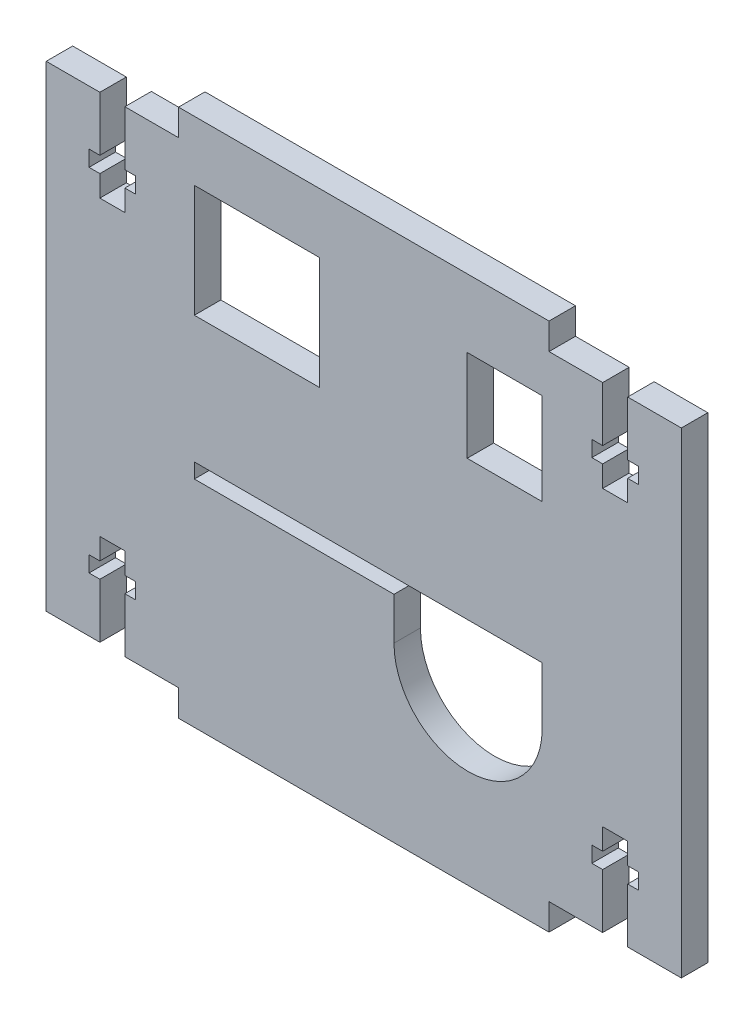
SolidWorks part; units mm, degrees
ref_plane "Front Plane" through (0, 0, 0) normal (0, 0, 1) x (1, 0, 0)
ref_plane "Top Plane" through (0, 0, 0) normal (0, 1, 0) x (1, 0, 0)
ref_plane "Right Plane" through (0, 0, 0) normal (1, 0, 0) x (0, 0, -1)
sketch "Sketch1" plane through (0, 0, 0) normal (0, 0, 1) x (1, 0, 0)
  line L1 (-38.1, -31.75) -> (38.1, -31.75)
  line L2 (-38.1, -31.75) -> (-38.1, 31.75)
  line L3 (-38.1, 31.75) -> (38.1, 31.75)
  line L4 (38.1, -31.75) -> (38.1, 31.75)
  line L5 (-38.1, -31.75) -> (38.1, 31.75) construction
  line L6 (-38.1, 31.75) -> (38.1, -31.75) construction
  point P0 (0, 0)
  dimension "D1" = 76.2
  dimension "D2" = 63.5
extrude "Boss-Extrude1" add sketch "Sketch1" along normal blind 3.175
sketch "Sketch2" plane through (0, 0, 0) normal (0, 0, -1) x (-1, 0, 0)
  line L0 (-38.1, 0) -> (38.1, 0) construction
  line L1 (-38.1, -31.75) -> (-22.225, -31.75)
  line L2 (-38.1, -31.75) -> (-38.1, -28.575)
  line L3 (-38.1, -28.575) -> (-22.225, -28.575)
  line L4 (-22.225, -31.75) -> (-22.225, -28.575)
  line L5 (38.1, -31.75) -> (22.225, -31.75)
  line L6 (38.1, -31.75) -> (38.1, -28.575)
  line L7 (38.1, -28.575) -> (22.225, -28.575)
  line L8 (22.225, -31.75) -> (22.225, -28.575)
  line L9 (-38.1, -31.75) -> (-38.1, 31.75) construction
  line L10 (38.1, 31.75) -> (38.1, -31.75) construction
  line L11 (22.225, 31.75) -> (22.225, 28.575)
  line L12 (38.1, 28.575) -> (22.225, 28.575)
  line L13 (38.1, 31.75) -> (38.1, 28.575)
  line L14 (38.1, 31.75) -> (22.225, 31.75)
  line L15 (-22.225, 31.75) -> (-22.225, 28.575)
  line L16 (-38.1, 28.575) -> (-22.225, 28.575)
  line L17 (-38.1, 31.75) -> (-38.1, 28.575)
  line L18 (-38.1, 31.75) -> (-22.225, 31.75)
  dimension "D1" = 3.175
  dimension "D2" = 44.45
extrude "Cut-Extrude1" cut sketch "Sketch2" against normal through all
sketch "Sketch3" plane through (0, 0, 3.175) normal (0, 0, 1) x (1, 0, 0)
  line L0 (31.6625, -17.575) -> (31.6625, -20.125)
  line L1 (31.6625, -17.575) -> (28.6625, -17.575)
  line L2 (31.6625, -28.575) -> (28.6625, -28.575)
  line L3 (28.6625, -17.575) -> (28.6625, -20.125)
  line L4 (31.6625, -17.575) -> (28.6625, -28.575) construction
  line L5 (31.6625, -28.575) -> (28.6625, -17.575) construction
  line L6 (28.6625, -22.025) -> (28.6625, -28.575)
  line L7 (27.3625, -22.025) -> (27.3625, -20.125)
  line L8 (27.3625, -22.025) -> (28.6625, -22.025)
  line L9 (32.9625, -22.025) -> (32.9625, -20.125)
  line L10 (27.3625, -20.125) -> (28.6625, -20.125)
  line L11 (27.3625, -22.025) -> (32.9625, -20.125) construction
  line L12 (32.9625, -22.025) -> (27.3625, -20.125) construction
  line L13 (31.6625, -22.025) -> (31.6625, -28.575)
  line L14 (28.6625, -20.125) -> (28.6625, -22.025) construction
  line L15 (31.6625, -17.575) -> (31.6625, -22.025) construction
  line L16 (31.6625, -22.025) -> (32.9625, -22.025)
  line L17 (31.6625, -20.125) -> (32.9625, -20.125)
  line L18 (28.6625, -20.125) -> (31.6625, -20.125) construction
  line L19 (31.6625, -22.025) -> (28.6625, -22.025) construction
  line L20 (22.225, -28.575) -> (38.1, -28.575) construction
  line L21 (0, 31.75) -> (0, -31.75) construction
  line L22 (22.225, 31.75) -> (-22.225, 31.75) construction
  line L23 (-22.225, -31.75) -> (22.225, -31.75) construction
  line L24 (-31.6625, -22.025) -> (-28.6625, -22.025) construction
  line L25 (-28.6625, -20.125) -> (-31.6625, -20.125) construction
  line L26 (-31.6625, -17.575) -> (-31.6625, -22.025) construction
  line L27 (-28.6625, -20.125) -> (-28.6625, -22.025) construction
  line L28 (-32.9625, -22.025) -> (-27.3625, -20.125) construction
  line L29 (-27.3625, -22.025) -> (-32.9625, -20.125) construction
  line L30 (-31.6625, -28.575) -> (-28.6625, -17.575) construction
  line L31 (-31.6625, -17.575) -> (-28.6625, -28.575) construction
  line L32 (-31.6625, -20.125) -> (-32.9625, -20.125)
  line L33 (-31.6625, -22.025) -> (-32.9625, -22.025)
  line L34 (-31.6625, -22.025) -> (-31.6625, -28.575)
  line L35 (-27.3625, -20.125) -> (-28.6625, -20.125)
  line L36 (-32.9625, -22.025) -> (-32.9625, -20.125)
  line L37 (-27.3625, -22.025) -> (-28.6625, -22.025)
  line L38 (-27.3625, -22.025) -> (-27.3625, -20.125)
  line L39 (-28.6625, -22.025) -> (-28.6625, -28.575)
  line L40 (-28.6625, -17.575) -> (-28.6625, -20.125)
  line L41 (-31.6625, -28.575) -> (-28.6625, -28.575)
  line L42 (-31.6625, -17.575) -> (-28.6625, -17.575)
  line L43 (-31.6625, -17.575) -> (-31.6625, -20.125)
  line L44 (-38.1, 0) -> (38.1, 0) construction
  line L45 (-38.1, 28.575) -> (-38.1, -28.575) construction
  line L46 (38.1, -28.575) -> (38.1, 28.575) construction
  line L47 (31.6625, 22.025) -> (28.6625, 22.025) construction
  line L48 (28.6625, 20.125) -> (31.6625, 20.125) construction
  line L49 (31.6625, 17.575) -> (31.6625, 22.025) construction
  line L50 (28.6625, 20.125) -> (28.6625, 22.025) construction
  line L51 (32.9625, 22.025) -> (27.3625, 20.125) construction
  line L52 (27.3625, 22.025) -> (32.9625, 20.125) construction
  line L53 (31.6625, 28.575) -> (28.6625, 17.575) construction
  line L54 (31.6625, 17.575) -> (28.6625, 28.575) construction
  line L55 (31.6625, 20.125) -> (32.9625, 20.125)
  line L56 (31.6625, 22.025) -> (32.9625, 22.025)
  line L57 (31.6625, 22.025) -> (31.6625, 28.575)
  line L58 (27.3625, 20.125) -> (28.6625, 20.125)
  line L59 (32.9625, 22.025) -> (32.9625, 20.125)
  line L60 (27.3625, 22.025) -> (28.6625, 22.025)
  line L61 (27.3625, 22.025) -> (27.3625, 20.125)
  line L62 (28.6625, 22.025) -> (28.6625, 28.575)
  line L63 (28.6625, 17.575) -> (28.6625, 20.125)
  line L64 (31.6625, 28.575) -> (28.6625, 28.575)
  line L65 (31.6625, 17.575) -> (28.6625, 17.575)
  line L66 (31.6625, 17.575) -> (31.6625, 20.125)
  line L67 (-31.6625, 17.575) -> (-28.6625, 28.575) construction
  line L68 (-31.6625, 28.575) -> (-28.6625, 17.575) construction
  line L69 (-27.3625, 22.025) -> (-32.9625, 20.125) construction
  line L70 (-32.9625, 22.025) -> (-27.3625, 20.125) construction
  line L71 (-28.6625, 20.125) -> (-28.6625, 22.025) construction
  line L72 (-31.6625, 17.575) -> (-31.6625, 22.025) construction
  line L73 (-28.6625, 20.125) -> (-31.6625, 20.125) construction
  line L74 (-31.6625, 22.025) -> (-28.6625, 22.025) construction
  line L75 (-31.6625, 17.575) -> (-31.6625, 20.125)
  line L76 (-31.6625, 17.575) -> (-28.6625, 17.575)
  line L77 (-31.6625, 28.575) -> (-28.6625, 28.575)
  line L78 (-28.6625, 17.575) -> (-28.6625, 20.125)
  line L79 (-28.6625, 22.025) -> (-28.6625, 28.575)
  line L80 (-27.3625, 22.025) -> (-27.3625, 20.125)
  line L81 (-27.3625, 22.025) -> (-28.6625, 22.025)
  line L82 (-32.9625, 22.025) -> (-32.9625, 20.125)
  line L83 (-27.3625, 20.125) -> (-28.6625, 20.125)
  line L84 (-31.6625, 22.025) -> (-31.6625, 28.575)
  line L85 (-31.6625, 22.025) -> (-32.9625, 22.025)
  line L86 (-31.6625, 20.125) -> (-32.9625, 20.125)
  point P0 (30.1625, -28.575)
  point P5 (30.1625, -21.075)
  point P35 (-30.1625, -21.075)
  point P36 (-30.1625, -28.575)
  point P55 (30.1625, 21.075)
  point P56 (30.1625, 28.575)
  point P69 (-30.1625, 28.575)
  point P70 (-30.1625, 21.075)
  dimension "D1" = 11
  dimension "D2" = 5.6
  dimension "D3" = 1.9
  dimension "D4" = 3.5
  dimension "D5" = 3
extrude "Cut-Extrude2" cut sketch "Sketch3" against normal through all
sketch "Sketch4" plane through (0, 0, 3.175) normal (0, 0, 1) x (1, 0, 0)
  line L0 (-18.0257, 12.575) -> (-7.6257, 12.575) construction
  line L1 (-20.3257, 11.075) -> (-5.3257, 11.075)
  line L2 (-20.3257, 11.075) -> (-20.3257, 24.575)
  line L3 (-20.3257, 24.575) -> (-5.3257, 24.575)
  line L4 (-5.3257, 11.075) -> (-5.3257, 24.575)
  line L5 (-18.8257, 12.975) -> (-18.8257, 23.075) construction
  line L6 (-6.8257, 12.975) -> (-6.8257, 23.075) construction
  line L7 (-18.5257, 23.075) -> (-7.1257, 23.075) construction
  line L8 (21.4041, 12.575) -> (12.4041, 12.575) construction
  line L9 (21.4041, 12.575) -> (12.4041, 12.575)
  line L10 (21.4041, 12.575) -> (21.4041, 23.575)
  line L11 (21.4041, 23.575) -> (12.4041, 23.575)
  line L12 (12.4041, 12.575) -> (12.4041, 23.575)
  line L13 (21.4041, 23.575) -> (21.4041, 12.575) construction
  line L14 (12.4041, 12.575) -> (12.4041, 23.575) construction
  line L15 (12.4041, 23.575) -> (21.4041, 23.575) construction
  dimension "D1" = 1.5
  dimension "D2" = 1.5
  dimension "D3" = 1.5
  dimension "D4" = 1.5
  dimension "D5" = 0
  dimension "D6" = 0
  dimension "D7" = 0
  dimension "D8" = 0
extrude "Cut-Extrude3" cut sketch "Sketch4" against normal through all
sketch "Sketch5" plane through (0, 0, 3.175) normal (0, 0, 1) x (1, 0, 0)
  line L0 (-20.3257, 24.575) -> (-20.3257, 11.075) construction
  line L1 (-20.3257, -5.943) -> (3.6241, -5.943)
  line L2 (-20.3257, -5.943) -> (-20.3257, -4.165)
  line L3 (-20.3257, -4.165) -> (21.4041, -4.165)
  line L4 (21.4041, -7.975) -> (21.4041, -4.165)
  line L6 (3.6241, -5.943) -> (3.6241, -11.023)
  line L7 (3.6241, -11.023) -> (21.4041, -11.023) construction
  line L8 (21.4041, -7.975) -> (21.4041, -11.023)
  line L9 (21.4041, 12.575) -> (21.4041, 23.575) construction
  line L10 (-20.3257, 11.075) -> (-5.3257, 11.075) construction
  arc A0 (3.6241, -11.023) -> (21.4041, -11.023) centre (12.5141, -11.023) ccw
  dimension "D1" = 1.778
  dimension "D2" = 5.08
  dimension "D3" = 17.78
  dimension "D5" = 15.24
extrude "Cut-Extrude4" cut sketch "Sketch5" against normal through all
